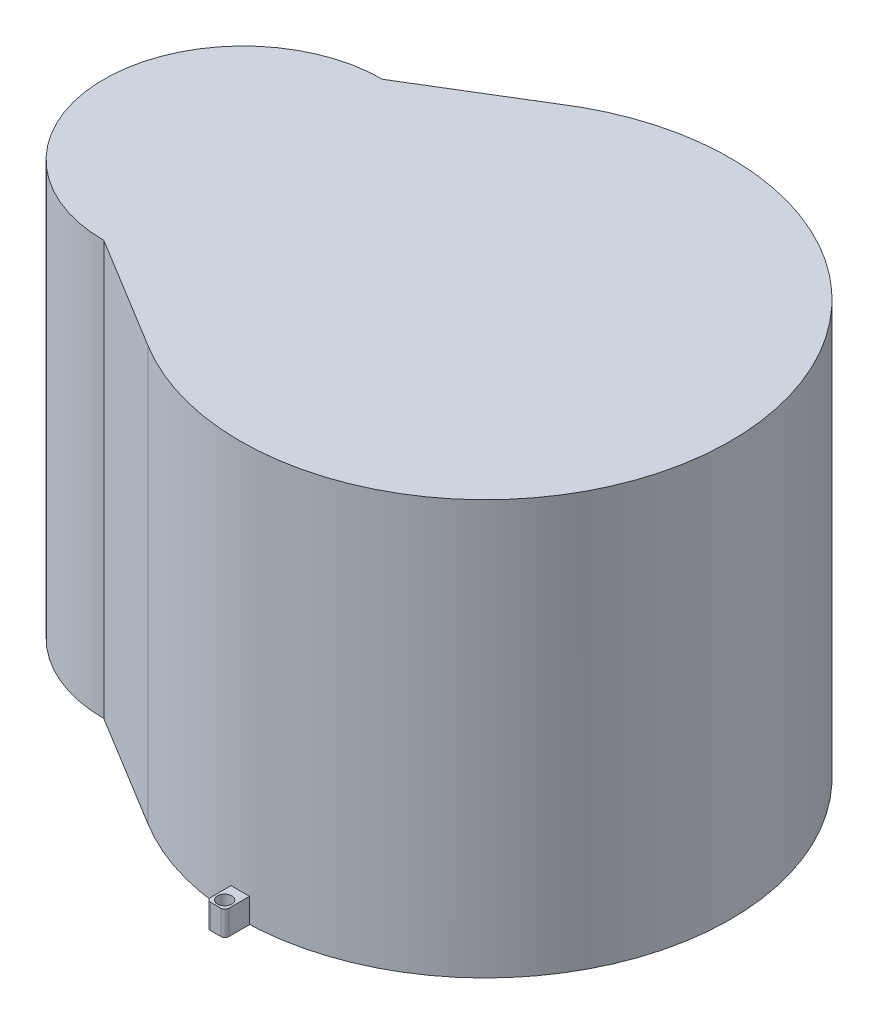
SolidWorks part; units mm, degrees
ref_plane "Front Plane" through (0, 0, 0) normal (0, 0, 1) x (1, 0, 0)
ref_plane "Top Plane" through (0, 0, 0) normal (0, 1, 0) x (1, 0, 0)
ref_plane "Right Plane" through (0, 0, 0) normal (1, 0, 0) x (0, 0, -1)
sketch "Sketch1" plane through (0, 0, 0) normal (0, 1, 0) x (1, 0, 0)
  line L0 (-41.9725, 26) -> (-11.1202, 42.3604)
  line L1 (-41.9725, -26) -> (-11.1202, -42.3604)
  line L2 (-41.9725, 21) -> (-8.1235, 36.7093)
  line L3 (-41.9725, -21) -> (-11.1202, -34.4606)
  line L4 (-41.9725, 34) -> (-15.7427, 49.9615)
  line L5 (-41.9725, -34) -> (-14.3535, -50.847)
  circle A0 centre (17.0825, 0) radius 44.53
  circle A1 centre (-41.9725, 0) radius 4.5
  circle A2 centre (17.0825, 0) radius 4.5
  circle A3 centre (17.0825, 0) radius 50.89
  arc A4 (-41.9725, -26) -> (-41.9725, 26) centre (-41.9725, 0) cw
  arc A5 (-41.9725, 21) -> (-41.9725, -21) centre (-41.9725, 0) ccw
  arc A6 (-41.9725, 34) -> (-41.9725, -34) centre (-41.9725, 0) ccw
  circle A7 centre (17.0825, 0) radius 59.78
extrude "Boss-Extrude1" add sketch "Sketch1" along normal blind 6 contours A7 L4 A6 L5 L1 A4 L0 | A7 L0 A4 L1 L3 A5 L2 | A7 L2 A5 L3 A1 | A0 A2 | L2 A7 A1 L3 A3 | L0 A7 L2 A3 | A7 L0 A3 L1 | L3 A7 L1 A3 | L2 A3 L3 A0 | A3 L2 A0 L3 | A2 | A1 region at (-69.154, 0, 0) region at (-38.0217, 0, -27.3215) region at (-25.2158, 0, -39.8955) region at (-27.6164, 0, -30.9806) region at (40.4577, 0, -43.6446) region at (-50.7163, 0, -0.0062) region at (-35.4912, 0, -0.2312) region at (-27.7124, 0, 30.8061) region at (-16.1116, 0, -32.168) region at (37.2382, 0, -38.2895)
extrude "Boss-Extrude2" add sketch "Sketch1<4>" against normal blind 85 contours A7 L0 A3 L1 | A7 L4 A6 L5 L1 A4 L0 region at (-69.154, 0, 0) region at (-25.2158, 0, -39.8955)
sketch "Sketch1<4>" plane through (0, 0, 0) normal (0, 1, 0) x (1, 0, 0) same geometry as "Sketch1"
sketch "Sketch3" plane through (0, 0, 0) normal (1, 0, 0) x (0, 0, -1)
  line L1 (0, 6) -> (0, -4)
  line L7 (59.78, 6) -> (-59.78, 6) construction
  line L8 (0, -4) -> (-8, -4)
  line L9 (0, -4) -> (8, -4)
  line L10 (8, -4) -> (8, -20)
  line L11 (8, -20) -> (-8, -20)
  line L12 (-8, -20) -> (-8, -4)
extrude "Cut-Extrude1" cut sketch "Sketch3" against normal blind 85 contours L12 L11 L10 L9 L8 region at (0, -12, 0)
sketch "Sketch4" plane through (0, -85, 0) normal (0, -1, 0) x (1, 0, 0)
  line L0 (76.8625, 0) -> (82.8625, 0)
  line L1 (82.8625, 0) -> (82.8625, 2.25)
  line L2 (82.8625, 0) -> (82.8625, -2.25)
  line L3 (82.8625, -2.25) -> (76.8201, -2.25)
  line L4 (82.8625, 2.25) -> (76.8201, 2.25)
  line L5 (-75.9725, 0) -> (-81.9725, 0)
  line L6 (-81.9725, 0) -> (-81.9725, 2.25)
  line L7 (-81.9725, 2.25) -> (-75.898, 2.25)
  line L8 (-81.9725, 0) -> (-81.9725, -2.25)
  line L9 (-81.9725, -2.25) -> (-75.898, -2.25)
  line L10 (17.0825, -59.78) -> (17.0825, -65.78)
  line L11 (17.0825, -59.78) -> (19.3325, -59.7376)
  line L12 (19.3325, -59.7376) -> (19.3325, -65.78)
  line L13 (17.0825, -65.78) -> (14.8325, -65.78)
  line L14 (14.8325, -65.78) -> (14.8325, -59.78)
  line L15 (14.8325, -59.78) -> (17.0825, -59.78)
  line L16 (19.3325, -65.78) -> (17.0825, -65.78)
  line L17 (17.0825, 59.78) -> (17.0825, 65.78)
  line L18 (17.0825, 65.78) -> (19.3325, 65.78)
  line L19 (19.3325, 65.78) -> (19.3325, 59.78)
  line L20 (19.3325, 59.78) -> (17.0825, 59.78)
  line L21 (17.0825, 59.78) -> (14.8325, 59.7376)
  line L22 (14.8325, 59.7376) -> (14.8325, 65.78)
  line L23 (14.8325, 65.78) -> (17.0825, 65.78)
  circle A0 centre (80.6625, 0) radius 1.75
  circle A2 centre (-79.7725, 0) radius 1.75
  arc A4 (-41.9725, 34) -> (-41.9725, -34) centre (-41.9725, 0) ccw construction
  arc A6 (-15.7427, -49.9615) -> (-14.3535, 50.847) centre (17.0825, 0) ccw construction
  arc A7 (17.0825, -59.78) -> (17.0825, 59.78) centre (17.0825, 0) ccw
  circle A8 centre (17.0825, -63.58) radius 1.75
  circle A9 centre (17.0825, 63.58) radius 1.75
  dimension "D1" = 6.0745
  dimension "D3" = 3.8
  dimension "D2" = 3.8
  dimension "D11" = 3.8
  dimension "D12" = 3.8
  dimension "D4" = 6.0424
  dimension "D5" = 2.2
  dimension "D6" = 6
  dimension "D7" = 6
  dimension "D8" = 2.25
  dimension "D9" = 2.25
  dimension "D10" = 2.25
fillet "Fillet2" radius 5 4 edges at (-75.0179, -12, 8) (-75.9725, -4, 0) (-75.0179, -12, -8) (-75.9725, -20, 0)
sketch "Sketch5" plane through (0, 0, 0) normal (0, -1, 0) x (1, 0, 0)
  line L0 (-41.9725, 26) -> (-11.1202, 42.3604)
  line L1 (-41.9725, -26) -> (-11.1202, -42.3604)
  arc A0 (-41.9725, -26) -> (-41.9725, 26) centre (-41.9725, 0) cw
  arc A1 (-41.9725, 26) -> (-41.9725, -26) centre (-41.9725, 0) ccw construction
  arc A2 (-41.9725, 26) -> (-41.9725, -26) centre (-41.9725, 0) ccw construction
  circle A3 centre (17.0825, 0) radius 50.89
  line M2 (-11.1202, 42.3604) -> (-41.9725, 26)
  arc M3 (-41.9725, 26) -> (-41.9725, -26) centre (-41.9725, 0) ccw
  line M4 (-41.9725, -26) -> (-11.1202, -42.3604)
  arc M5 (-11.1202, -42.3604) -> (-11.1202, 42.3604) centre (17.0825, 0) ccw
extrude "Boss-Extrude5" add sketch "Sketch5" along normal blind 85 contours A3 M2 M3 M4 | A3 M5 region at (-45.1414, 0, 0) region at (17.0825, 0, 0)
extrude "Cut-Extrude2" cut sketch "Sketch5<4>" along normal blind 79 contours A3 M5 | A3 M2 M3 M4 region at (-45.1414, 0, 0) region at (17.0825, 0, 0)
sketch "Sketch5<4>" plane through (0, 0, 0) normal (0, -1, 0) x (1, 0, 0) same geometry as "Sketch5"
sketch "Sketch7" plane through (0, -85, 0) normal (0, -1, 0) x (1, 0, 0)
  line L0 (-41.9725, 34) -> (-14.3535, 50.847) construction
  line L1 (-41.9725, 26) -> (-11.1248, 42.3573)
  line L2 (-63.9725, 22) -> (-19.9725, 22)
  line L3 (-63.9725, 22) -> (-63.9725, -22)
  line L4 (-63.9725, -22) -> (-19.9725, -22)
  line L5 (-19.9725, 22) -> (-19.9725, -22)
  line L6 (-63.9725, 22) -> (-19.9725, -22) construction
  line L7 (-63.9725, -22) -> (-19.9725, 22) construction
  line L8 (-41.9725, -26) -> (-11.1248, -42.3573)
  line L9 (-19.9725, 22) -> (60.0275, 22)
  line L10 (60.0275, 22) -> (60.0275, -22)
  line L11 (60.0275, -22) -> (-19.9725, -22)
  arc A0 (-41.9725, -34) -> (-41.9725, 34) centre (-41.9725, 0) cw
  arc A1 (-41.9725, -26) -> (-41.9725, 26) centre (-41.9725, 0) cw
  circle A2 centre (17.0825, 0) radius 50.89
  arc M6 (-15.7427, -49.9615) -> (-14.3535, 50.847) centre (17.0825, 0) ccw
  line M7 (-14.3535, 50.847) -> (-41.9725, 34)
  arc M8 (-41.9725, 34) -> (-41.9725, -34) centre (-41.9725, 0) ccw
  arc M13 (-41.9725, 34) -> (-41.9725, -34) centre (-41.9725, 0) ccw
  line M14 (-41.9725, -34) -> (-15.7427, -49.9615)
  arc M15 (-15.7427, -49.9615) -> (-14.3535, 50.847) centre (17.0825, 0) ccw
  dimension "D3" = 80
  dimension "D1" = 44
  dimension "D2" = 44
  dimension "D4" = 42.945
extrude "Cut-Extrude5" cut sketch "Sketch7" against normal blind 85 contours L5 L2 L3 L4 | L3 L2 L5 L4 region at (-26.1633, -85, 0)
extrude "Boss-Extrude7" add sketch "Sketch7<6>" along normal blind 10 contours A0 A2 L8 A1 L4 L3 L2 L1 M13 M14 M15 M6 M7 M8 region at (-74.0321, -85, 0)
sketch "Sketch7<6>" plane through (0, -85, 0) normal (0, -1, 0) x (1, 0, 0) same geometry as "Sketch7"
extrude "Cut-Extrude6" cut sketch "Sketch7<7>" against normal blind 7 contours L11 L10 L9 L5 region at (20.0275, -85, 0)
sketch "Sketch7<7>" plane through (0, -85, 0) normal (0, -1, 0) x (1, 0, 0) same geometry as "Sketch7"
sketch "Sketch9" plane through (0, -95, 0) normal (0, -1, 0) x (1, 0, 0)
  line L0 (-75.9725, 0) -> (-81.9725, 0)
  line L1 (-81.9725, 0) -> (-81.9725, -2.25)
  line L2 (-81.9725, -2.25) -> (-75.898, -2.25)
  line L3 (-81.9725, 0) -> (-81.9725, 2.25)
  line L4 (-81.9725, 2.25) -> (-75.898, 2.25)
  line L5 (76.8625, 0) -> (82.8625, 0)
  line L6 (82.8625, 0) -> (82.8625, -2.25)
  line L7 (82.8625, -2.25) -> (76.8201, -2.25)
  line L8 (76.8201, 2.25) -> (82.8625, 2.25)
  line L9 (82.8625, 2.25) -> (82.8625, 0)
  line L11 (17.0825, 59.78) -> (19.3325, 59.78)
  line L12 (19.3325, 59.78) -> (19.3325, 65.78)
  line L13 (19.3325, 65.78) -> (17.0825, 65.78)
  line L14 (17.0825, 65.78) -> (14.8325, 65.78)
  line L15 (14.8325, 65.78) -> (14.8325, 59.7376)
  line L16 (14.8325, 59.7376) -> (17.0825, 59.78)
  line L17 (17.0825, 65.78) -> (17.0825, 59.78)
  line L18 (14.8325, -59.78) -> (19.3325, -59.7376)
  line L19 (19.3325, -59.7376) -> (19.3325, -65.78)
  line L20 (19.3325, -65.78) -> (14.8325, -65.78)
  line L21 (14.8325, -65.78) -> (14.8325, -59.78)
  line L22 (17.0825, -65.78) -> (17.0825, -59.78)
  circle A0 centre (80.6625, 0) radius 1.75
  circle A2 centre (-79.7725, 0) radius 1.75
  circle A4 centre (17.0825, 63.58) radius 1.75
  circle A5 centre (17.0825, -63.58) radius 1.75
  arc M12 (-15.7427, -49.9615) -> (-14.3535, 50.847) centre (17.0825, 0) ccw
  arc M14 (-41.9725, 34) -> (-41.9725, -34) centre (-41.9725, 0) ccw
  dimension "D1" = 3.8
  dimension "D2" = 3.8
  dimension "D3" = 6.0424
extrude "Boss-Extrude8" add sketch "Sketch9" against normal blind 6 contours L5 L7 L6 M12 | L5 L9 L8 M12 | A2 L0 L1 L2 M14 | A2 L0 L4 L3 M14 region at (-78.5131, -95, -1.3389) region at (-78.5131, -95, 1.3389) region at (79.4102, -95, 1.3379) region at (79.4102, -95, -1.3379)
extrude "Boss-Extrude9" add sketch "Sketch9<3>" against normal blind 6 contours A5 L22 L20 L19 M12 | A5 L22 L18 L21 L20 M12 | A4 L17 L14 L15 M12 | A4 L17 L11 L12 L13 region at (18.4204, -95, -62.3277) region at (15.7446, -95, 62.3277) region at (18.4191, -95, 62.3371) region at (15.746, -95, -62.3342)
sketch "Sketch9<3>" plane through (0, -95, 0) normal (0, -1, 0) x (1, 0, 0) same geometry as "Sketch9"
fillet "Fillet4" radius 1 6 edges at (-81.9725, -92, 2.25) (-81.9725, -92, -2.25) (19.3325, -92, 65.78) (14.8325, -92, 65.78) (19.3325, -92, -65.78) (14.8325, -92, -65.78)
extrude "Cut-Extrude7" cut sketch "Sketch9<4>" against normal blind 7 contours A0 L5 L9 L8 M12 | A0 L5 L7 L6 M12 region at (79.4102, -95, 1.3379) region at (79.4102, -95, -1.3379)
sketch "Sketch9<4>" plane through (0, -95, 0) normal (0, -1, 0) x (1, 0, 0) same geometry as "Sketch9"
